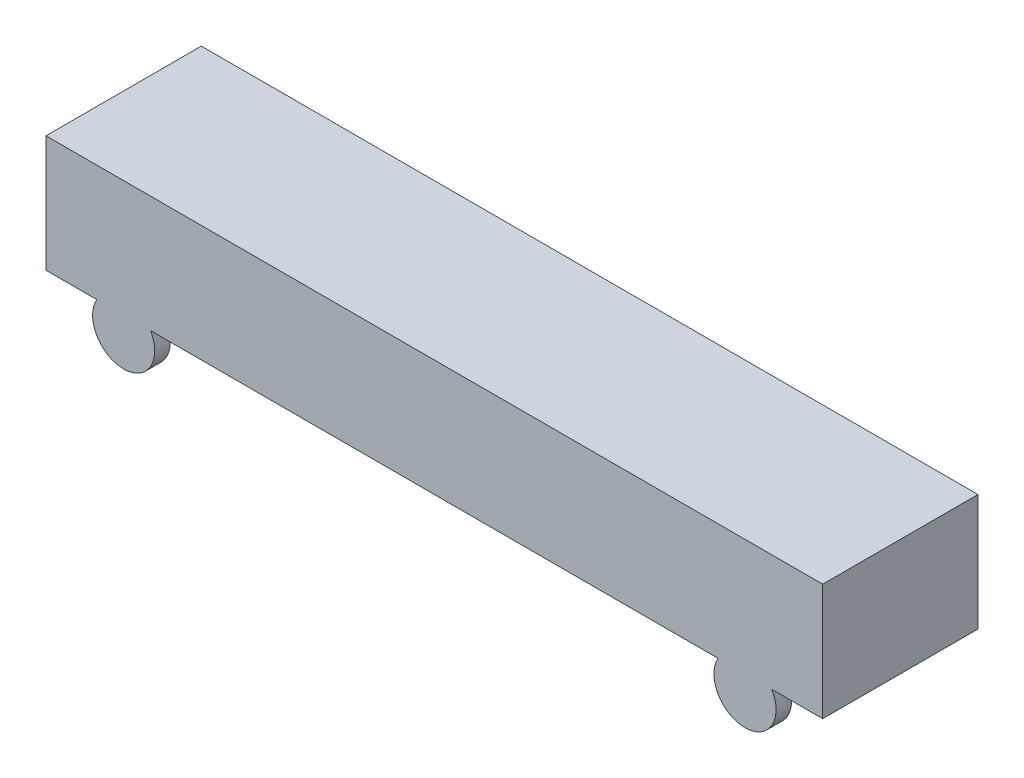
SolidWorks part; units mm, degrees
ref_plane "前视基准面" through (0, 0, 0) normal (0, 0, 1) x (1, 0, 0)
ref_plane "上视基准面" through (0, 0, 0) normal (0, 1, 0) x (1, 0, 0)
ref_plane "右视基准面" through (0, 0, 0) normal (1, 0, 0) x (0, 0, -1)
other "Configuration Table"
sketch "草图1" plane through (0, 0, 0) normal (0, 0, 1) x (1, 0, 0)
  line L1 (0, 0) -> (10, 0)
  line L2 (0, 0) -> (0, 1.5)
  line L3 (0, 1.5) -> (10, 1.5)
  line L4 (10, 0) -> (10, 1.5)
  dimension "D1" = 1.5
  dimension "D2" = 10
extrude "凸台-拉伸1" add sketch "草图1" along normal blind 1 and the other way blind 1
sketch "草图2" plane through (0, 0, 1) normal (0, 0, 1) x (1, 0, 0)
  line L0 (10, 0) -> (10, 1.5) construction
  line L1 (0, 0) -> (10, 0) construction
  circle A0 centre (9, -0.2) radius 0.4
  circle A1 centre (1, -0.2) radius 0.4
  dimension "D1" = 0.8
  dimension "D2" = 1
  dimension "D3" = 0.2
  dimension "D5" = 8
  dimension "D4" = 2
extrude "凸台-拉伸2" add sketch "草图2" against normal blind 0.2
mirror "镜向1" about plane through (0, 0, 0) normal (0, 0, 1) of "凸台-拉伸2"
